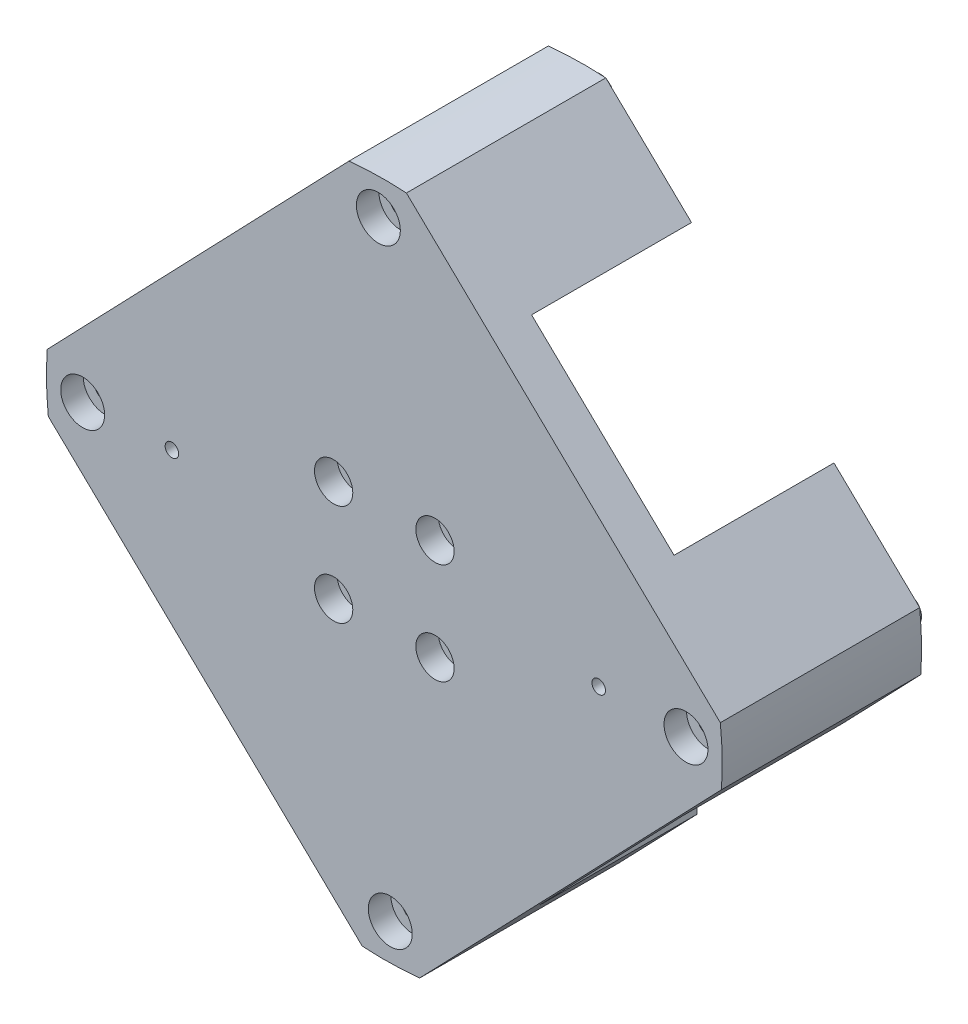
SolidWorks part; units mm, degrees
ref_plane "前视基准面" through (0, 0, 0) normal (0, 0, 1) x (1, 0, 0)
ref_plane "上视基准面" through (0, 0, 0) normal (0, 1, 0) x (1, 0, 0)
ref_plane "右视基准面" through (0, 0, 0) normal (1, 0, 0) x (0, 0, -1)
other "Configuration Table"
sketch "草图1" plane through (0, 0, 0) normal (0, 0, 1) x (1, 0, 0)
  circle A0 centre (9, 9) radius 2.6 construction
  circle A1 centre (9, -9) radius 2.6
  circle A2 centre (9, -9) radius 2.6
  circle A3 centre (0, 0) radius 60
  circle A4 centre (0, 0) radius 60
  circle A5 centre (9, 9) radius 1.4 construction
  circle A6 centre (-9, 9) radius 1.4 construction
  circle A7 centre (-9, 9) radius 2.6 construction
  circle A8 centre (-9, -9) radius 1.4 construction
  circle A9 centre (-9, -9) radius 2.6 construction
  circle A10 centre (9, 9) radius 2.6
  circle A11 centre (9, 9) radius 1.4
  circle A12 centre (-9, 9) radius 1.4
  circle A13 centre (-9, 9) radius 2.6
  circle A14 centre (-9, -9) radius 1.4
  circle A15 centre (-9, -9) radius 2.6
  circle A16 centre (9, -9) radius 1.4 construction
  circle A17 centre (9, -9) radius 1.4
  circle A18 centre (0, 0) radius 47.6 construction
  circle A19 centre (0, 0) radius 47.6
  circle A20 centre (53.5645, 1.0586) radius 2.425 construction
  circle A21 centre (53.5645, 1.0586) radius 2.425
  circle A22 centre (1.0586, -53.5645) radius 2.425 construction
  circle A23 centre (1.0586, -53.5645) radius 2.425
  circle A24 centre (-53.5645, -1.0586) radius 2.425 construction
  circle A25 centre (-53.5645, -1.0586) radius 2.425
  circle A26 centre (-1.0586, 53.5645) radius 2.425 construction
  circle A27 centre (-1.0586, 53.5645) radius 2.425
  dimension "D1" = 0
  dimension "D2" = 0
extrude "凸台-拉伸1" add sketch "草图1" along normal blind 3 contours A4 A27 A25 A23 A21 A19 | A19 A2 A10 A13 A15 region at (-58.3029, 0, 0) region at (0, 0, 0)
sketch "草图2" plane through (0, 0, 0) normal (0, 0, -1) x (-1, 0, 0)
  circle A0 centre (0, 0) radius 47.6 construction
  circle A1 centre (0, 0) radius 60
  circle A2 centre (0, 0) radius 60
  circle A3 centre (0, 0) radius 47.6
  circle A4 centre (1.0586, 53.5645) radius 2.425 construction
  circle A5 centre (1.0586, 53.5645) radius 2.425
  circle A6 centre (-53.5645, 1.0586) radius 2.425 construction
  circle A7 centre (-53.5645, 1.0586) radius 2.425
  circle A8 centre (-1.0586, -53.5645) radius 2.425 construction
  circle A9 centre (-1.0586, -53.5645) radius 2.425
  circle A10 centre (53.5645, -1.0586) radius 2.425 construction
  circle A11 centre (53.5645, -1.0586) radius 2.425
  dimension "D1" = 0
extrude "凸台-拉伸2" add sketch "草图2" along normal up to surface (28.4 mm away) contours A2 | A5 | A9 | A7 | A11 | A3
sketch "草图3" plane through (0, 0, 3) normal (0, 0, 1) x (1, 0, 0)
  line L0 (-53.5645, -1.0586) -> (-1.0586, 53.5645)
  line L1 (-53.5645, -1.0586) -> (1.0586, -53.5645)
  line L2 (-1.0586, 53.5645) -> (53.5645, 1.0586)
  line L3 (1.0586, -53.5645) -> (53.5645, 1.0586)
  line L4 (-64.876, -1.2822) -> (-1.2822, 64.876)
  line L5 (-1.2822, 64.876) -> (64.876, 1.2822)
  line L6 (1.2822, -64.876) -> (64.876, 1.2822)
  line L7 (-64.876, -1.2822) -> (1.2822, -64.876)
  circle A0 centre (53.5645, 1.0586) radius 2.425 construction
  circle A1 centre (0, 0) radius 60
  circle A2 centre (0, 0) radius 60
  circle A3 centre (53.5645, 1.0586) radius 2.425
  circle A4 centre (-1.0586, 53.5645) radius 2.425 construction
  circle A5 centre (-1.0586, 53.5645) radius 2.425
  circle A6 centre (-53.5645, -1.0586) radius 2.425 construction
  circle A7 centre (-53.5645, -1.0586) radius 2.425
  circle M10 centre (0, 0) radius 60
  dimension "D1" = 0
  dimension "D2" = 8
extrude "切除-拉伸1" cut sketch "草图3" against normal blind 31 contours L4 M10 | L7 M10 | L5 M10 | L6 M10 region at (-37.1941, 35.7524, 3) region at (-35.7524, -37.1941, 3) region at (35.7524, 37.1941, 3) region at (37.1941, -35.7524, 3)
sketch "草图4" plane through (0, 0, -28) normal (0, 0, 1) x (1, 0, 0)
  line L2 (40.9301, 24.3) -> (59.6697, 6.2867)
  line L3 (3.9241, 59.8715) -> (22.6638, 41.8583)
  line L4 (40.9301, 24.3) -> (59.6697, 6.2867)
  line L5 (3.9241, 59.8715) -> (22.6638, 41.8583)
  line L6 (24.3, -40.9301) -> (6.2867, -59.6697)
  line L7 (59.8715, -3.9241) -> (41.8583, -22.6638)
  line L8 (24.3, -40.9301) -> (6.2867, -59.6697)
  line L9 (59.8715, -3.9241) -> (41.8583, -22.6638)
  line L10 (-40.9301, -24.3) -> (-59.6697, -6.2867)
  line L11 (-3.9241, -59.8715) -> (-22.6638, -41.8583)
  line L12 (-40.9301, -24.3) -> (-59.6697, -6.2867)
  line L13 (-3.9241, -59.8715) -> (-22.6638, -41.8583)
  line L14 (-24.3, 40.9301) -> (-6.2867, 59.6697)
  line L15 (-59.8715, 3.9241) -> (-41.8583, 22.6638)
  line L16 (-24.3, 40.9301) -> (-6.2867, 59.6697)
  line L17 (-59.8715, 3.9241) -> (-41.8583, 22.6638)
  arc A2 (59.6697, 6.2867) -> (3.9241, 59.8715) centre (0, 0) ccw
  arc A3 (40.9301, 24.3) -> (22.6638, 41.8583) centre (0, 0) ccw
  arc A4 (59.6697, 6.2867) -> (3.9241, 59.8715) centre (0, 0) ccw
  arc A5 (40.9301, 24.3) -> (22.6638, 41.8583) centre (0, 0) ccw
  arc A6 (6.2867, -59.6697) -> (59.8715, -3.9241) centre (0, 0) ccw
  arc A7 (24.3, -40.9301) -> (41.8583, -22.6638) centre (0, 0) ccw
  arc A8 (6.2867, -59.6697) -> (59.8715, -3.9241) centre (0, 0) ccw
  arc A9 (24.3, -40.9301) -> (41.8583, -22.6638) centre (0, 0) ccw
  arc A10 (-59.6697, -6.2867) -> (-3.9241, -59.8715) centre (0, 0) ccw
  arc A11 (-40.9301, -24.3) -> (-22.6638, -41.8583) centre (0, 0) ccw
  arc A12 (-59.6697, -6.2867) -> (-3.9241, -59.8715) centre (0, 0) ccw
  arc A13 (-40.9301, -24.3) -> (-22.6638, -41.8583) centre (0, 0) ccw
  arc A14 (-6.2867, 59.6697) -> (-59.8715, 3.9241) centre (0, 0) ccw
  arc A15 (-24.3, 40.9301) -> (-41.8583, 22.6638) centre (0, 0) ccw
  arc A16 (-6.2867, 59.6697) -> (-59.8715, 3.9241) centre (0, 0) ccw
  arc A17 (-24.3, 40.9301) -> (-41.8583, 22.6638) centre (0, 0) ccw
  dimension "D1" = 0
  dimension "D2" = 0
  dimension "D3" = 0
  dimension "D4" = 0
extrude "切除-拉伸2" cut sketch "草图4" against normal up to next
chamfer "倒角1" distance 6 angle 45 8 edges at (-24.3, 40.9301, -14.2) (-41.8583, 22.6638, -14.2) (-40.9301, -24.3, -14.2) (-22.6638, -41.8583, -14.2) (24.3, -40.9301, -14.2) (41.8583, -22.6638, -14.2) (40.9301, 24.3, -14.2) (22.6638, 41.8583, -14.2) first distance on face at (-0.8793, 44.4924, -14.2) first distance on face at (-44.4924, -0.8793, -14.2) first distance on face at (-31.7969, -33.0791, -13.45) first distance on face at (33.0791, -31.7969, -13.45) first distance on face at (44.4924, 0.8793, -14.2)
sketch "草图6" plane through (0, 0, 3) normal (0, 0, 1) x (1, 0, 0)
  line L4 (-59.6697, -6.2867) -> (-3.9241, -59.8715)
  line L5 (6.2867, -59.6697) -> (59.8715, -3.9241)
  line L6 (59.6697, 6.2867) -> (3.9241, 59.8715)
  line L7 (-6.2867, 59.6697) -> (-59.8715, 3.9241)
  line L8 (-59.6697, -6.2867) -> (-3.9241, -59.8715)
  line L9 (6.2867, -59.6697) -> (59.8715, -3.9241)
  line L10 (59.6697, 6.2867) -> (3.9241, 59.8715)
  line L11 (-6.2867, 59.6697) -> (-59.8715, 3.9241)
  circle A0 centre (9, 9) radius 2.6 construction
  circle A1 centre (9, 9) radius 2.6
  circle A2 centre (9, -9) radius 2.6 construction
  circle A3 centre (9, -9) radius 2.6
  arc A4 (-59.8715, 3.9241) -> (-59.6697, -6.2867) centre (0, 0) ccw
  arc A5 (-3.9241, -59.8715) -> (6.2867, -59.6697) centre (0, 0) ccw
  arc A6 (59.8715, -3.9241) -> (59.6697, 6.2867) centre (0, 0) ccw
  arc A7 (3.9241, 59.8715) -> (-6.2867, 59.6697) centre (0, 0) ccw
  arc A8 (-59.8715, 3.9241) -> (-59.6697, -6.2867) centre (0, 0) ccw
  arc A9 (-3.9241, -59.8715) -> (6.2867, -59.6697) centre (0, 0) ccw
  arc A10 (59.8715, -3.9241) -> (59.6697, 6.2867) centre (0, 0) ccw
  arc A11 (3.9241, 59.8715) -> (-6.2867, 59.6697) centre (0, 0) ccw
  circle A12 centre (-9, -9) radius 2.6 construction
  circle A13 centre (-9, -9) radius 2.6
  circle A14 centre (-9, 9) radius 2.6 construction
  circle A15 centre (-9, 9) radius 2.6
  circle A16 centre (-9, 9) radius 1.4 construction
  circle A17 centre (-9, 9) radius 1.4
  circle A18 centre (9, 9) radius 1.4 construction
  circle A19 centre (9, 9) radius 1.4
  circle A20 centre (9, -9) radius 1.4 construction
  circle A21 centre (9, -9) radius 1.4
  circle A22 centre (-9, -9) radius 1.4 construction
  circle A23 centre (-9, -9) radius 1.4
  circle M17 centre (9, -9) radius 2.6
  circle M18 centre (9, 9) radius 2.6
  circle M19 centre (-9, 9) radius 2.6
  circle M20 centre (-9, -9) radius 2.6
  dimension "D1" = 0
extrude "凸台-拉伸4" add sketch "草图6" against normal up to surface (3 mm away) contours A19 M18 | A21 M17 | A23 M20 | A17 M19 region at (6.4735, 9, 3) region at (6.4735, -9, 3) region at (-11.5265, -9, 3) region at (-11.5265, 9, 3) up to face at (-6.4, -9, 0)
sketch "草图7" plane through (0, 0, 0) normal (0, 0, -1) x (-1, 0, 0)
  line L12 (18.3381, -46.0162) -> (45.2557, -20.142)
  line L13 (45.2557, -20.142) -> (43.1478, -20.1003)
  line L14 (44.5387, 16.7948) -> (45.2385, 19.1472)
  line L15 (45.2385, 19.1472) -> (20.9197, 44.4466)
  line L16 (20.9197, 44.4466) -> (18.5415, 43.8403)
  line L17 (-16.7948, 44.5387) -> (-19.1472, 45.2385)
  line L18 (-19.1472, 45.2385) -> (-44.4466, 20.9197)
  line L19 (-44.4466, 20.9197) -> (-43.8403, 18.5415)
  line L20 (-43.9084, -18.3798) -> (-46.0162, -18.3381)
  line L21 (-46.0162, -18.3381) -> (-20.142, -45.2557)
  line L22 (-20.142, -45.2557) -> (-20.1003, -43.1478)
  line L23 (18.3798, -43.9084) -> (18.3381, -46.0162)
  line L24 (18.3381, -46.0162) -> (45.2557, -20.142)
  line L25 (45.2557, -20.142) -> (43.1478, -20.1003)
  line L26 (44.5387, 16.7948) -> (45.2385, 19.1472)
  line L27 (45.2385, 19.1472) -> (20.9197, 44.4466)
  line L28 (20.9197, 44.4466) -> (18.5415, 43.8403)
  line L29 (-16.7948, 44.5387) -> (-19.1472, 45.2385)
  line L30 (-19.1472, 45.2385) -> (-44.4466, 20.9197)
  line L31 (-44.4466, 20.9197) -> (-43.8403, 18.5415)
  line L32 (-43.9084, -18.3798) -> (-46.0162, -18.3381)
  line L33 (-46.0162, -18.3381) -> (-20.142, -45.2557)
  line L34 (-20.142, -45.2557) -> (-20.1003, -43.1478)
  line L35 (18.3798, -43.9084) -> (18.3381, -46.0162)
  circle A0 centre (37.7185, -0.4693) radius 1.2 construction
  circle A1 centre (37.7185, -0.4693) radius 1.2
  circle A2 centre (-38.0667, 1.0285) radius 1.2 construction
  circle A3 centre (-38.0667, 1.0285) radius 1.2
  arc A4 (43.1478, -20.1003) -> (44.5387, 16.7948) centre (0, 0) ccw
  arc A5 (18.5415, 43.8403) -> (-16.7948, 44.5387) centre (0, 0) ccw
  arc A6 (-43.8403, 18.5415) -> (-43.9084, -18.3798) centre (0, 0) ccw
  arc A7 (-20.1003, -43.1478) -> (18.3798, -43.9084) centre (0, 0) ccw
  arc A8 (43.1478, -20.1003) -> (44.5387, 16.7948) centre (0, 0) ccw
  arc A9 (18.5415, 43.8403) -> (-16.7948, 44.5387) centre (0, 0) ccw
  arc A10 (-43.8403, 18.5415) -> (-43.9084, -18.3798) centre (0, 0) ccw
  arc A11 (-20.1003, -43.1478) -> (18.3798, -43.9084) centre (0, 0) ccw
  dimension "D1" = 0
extrude "切除-拉伸3" cut sketch "草图7" against normal blind 10 contours A1 | A3
sketch "草图8" plane through (0, 0, 3) normal (0, 0, 1) x (1, 0, 0)
  line L4 (-59.6697, -6.2867) -> (-3.9241, -59.8715)
  line L5 (6.2867, -59.6697) -> (59.8715, -3.9241)
  line L6 (59.6697, 6.2867) -> (3.9241, 59.8715)
  line L7 (-6.2867, 59.6697) -> (-59.8715, 3.9241)
  line L8 (-59.6697, -6.2867) -> (-3.9241, -59.8715)
  line L9 (6.2867, -59.6697) -> (59.8715, -3.9241)
  line L10 (59.6697, 6.2867) -> (3.9241, 59.8715)
  line L11 (-6.2867, 59.6697) -> (-59.8715, 3.9241)
  circle A0 centre (-1.0586, 53.5645) radius 2.425 construction
  circle A1 centre (-1.0586, 53.5645) radius 2.425
  circle A2 centre (53.5645, 1.0586) radius 2.425 construction
  circle A3 centre (53.5645, 1.0586) radius 2.425
  arc A4 (-59.8715, 3.9241) -> (-59.6697, -6.2867) centre (0, 0) ccw
  arc A5 (-3.9241, -59.8715) -> (6.2867, -59.6697) centre (0, 0) ccw
  arc A6 (59.8715, -3.9241) -> (59.6697, 6.2867) centre (0, 0) ccw
  arc A7 (3.9241, 59.8715) -> (-6.2867, 59.6697) centre (0, 0) ccw
  arc A8 (-59.8715, 3.9241) -> (-59.6697, -6.2867) centre (0, 0) ccw
  arc A9 (-3.9241, -59.8715) -> (6.2867, -59.6697) centre (0, 0) ccw
  arc A10 (59.8715, -3.9241) -> (59.6697, 6.2867) centre (0, 0) ccw
  arc A11 (3.9241, 59.8715) -> (-6.2867, 59.6697) centre (0, 0) ccw
  circle A12 centre (1.0586, -53.5645) radius 2.425 construction
  circle A13 centre (1.0586, -53.5645) radius 2.425
  circle A14 centre (-53.5645, -1.0586) radius 2.425 construction
  circle A15 centre (-53.5645, -1.0586) radius 2.425
  circle A16 centre (-1.0586, 53.5645) radius 1.9
  circle A17 centre (-53.5645, -1.0586) radius 1.9
  circle A18 centre (53.5645, 1.0586) radius 1.9
  circle A19 centre (1.0586, -53.5645) radius 1.9
  circle M12 centre (-1.0586, 53.5645) radius 2.425
  circle M13 centre (-53.5645, -1.0586) radius 2.425
  circle M14 centre (1.0586, -53.5645) radius 2.425
  circle M15 centre (53.5645, 1.0586) radius 2.425
  dimension "D2" = 3.8
  dimension "D3" = 3.8
  dimension "D4" = 3.8
  dimension "D5" = 3.8
  dimension "D1" = 0
extrude "凸台-拉伸5" add sketch "草图8" against normal offset from surface (35.4 mm away) 4 contours A16 M12 | A17 M13 | A19 M14 | A18 M15 region at (-3.415, 53.5645, 3) region at (51.2081, 1.0586, 3) region at (-1.2978, -53.5645, 3) region at (-55.921, -1.0586, 3) up to face at (-50.2771, -1.1346, -28.4) offset beyond the face yes
sketch "草图9" plane through (0, 0, 3) normal (0, 0, 1) x (1, 0, 0)
  line L4 (-59.6697, -6.2867) -> (-3.9241, -59.8715)
  line L5 (6.2867, -59.6697) -> (59.8715, -3.9241)
  line L6 (59.6697, 6.2867) -> (3.9241, 59.8715)
  line L7 (-6.2867, 59.6697) -> (-59.8715, 3.9241)
  line L8 (-59.6697, -6.2867) -> (-3.9241, -59.8715)
  line L9 (6.2867, -59.6697) -> (59.8715, -3.9241)
  line L10 (59.6697, 6.2867) -> (3.9241, 59.8715)
  line L11 (-6.2867, 59.6697) -> (-59.8715, 3.9241)
  circle A0 centre (-1.0586, 53.5645) radius 1.9 construction
  circle A1 centre (-1.0586, 53.5645) radius 1.9
  circle A2 centre (-53.5645, -1.0586) radius 1.9 construction
  circle A3 centre (-53.5645, -1.0586) radius 1.9
  arc A4 (-59.8715, 3.9241) -> (-59.6697, -6.2867) centre (0, 0) ccw
  arc A5 (-3.9241, -59.8715) -> (6.2867, -59.6697) centre (0, 0) ccw
  arc A6 (59.8715, -3.9241) -> (59.6697, 6.2867) centre (0, 0) ccw
  arc A7 (3.9241, 59.8715) -> (-6.2867, 59.6697) centre (0, 0) ccw
  arc A8 (-59.8715, 3.9241) -> (-59.6697, -6.2867) centre (0, 0) ccw
  arc A9 (-3.9241, -59.8715) -> (6.2867, -59.6697) centre (0, 0) ccw
  arc A10 (59.8715, -3.9241) -> (59.6697, 6.2867) centre (0, 0) ccw
  arc A11 (3.9241, 59.8715) -> (-6.2867, 59.6697) centre (0, 0) ccw
  circle A12 centre (1.0586, -53.5645) radius 1.9 construction
  circle A13 centre (1.0586, -53.5645) radius 1.9
  circle A14 centre (53.5645, 1.0586) radius 1.9 construction
  circle A15 centre (53.5645, 1.0586) radius 1.9
  circle A16 centre (9, 9) radius 1.4 construction
  circle A17 centre (9, 9) radius 1.4
  circle A18 centre (-9, 9) radius 1.4 construction
  circle A19 centre (-9, 9) radius 1.4
  circle A20 centre (-9, -9) radius 1.4 construction
  circle A21 centre (-9, -9) radius 1.4
  circle A22 centre (9, -9) radius 1.4 construction
  circle A23 centre (9, -9) radius 1.4
  circle A24 centre (-37.7185, -0.4693) radius 1.2 construction
  circle A25 centre (-37.7185, -0.4693) radius 1.2
  circle A26 centre (38.0667, 1.0285) radius 1.2 construction
  circle A27 centre (38.0667, 1.0285) radius 1.2
  circle A28 centre (-53.5645, -1.0586) radius 3.9
  circle A29 centre (-1.0586, 53.5645) radius 3.9
  circle A30 centre (53.5645, 1.0586) radius 3.9
  circle A31 centre (9, 9) radius 3.4
  circle A32 centre (-9, 9) radius 3.4
  circle A33 centre (-9, -9) radius 3.4
  circle A34 centre (9, -9) radius 3.4
  circle A35 centre (1.0586, -53.5645) radius 3.9
  circle M12 centre (-37.7185, -0.4693) radius 1.2
  circle M13 centre (38.0667, 1.0285) radius 1.2
  arc M14 (-59.8715, 3.9241) -> (-59.6697, -6.2867) centre (0, 0) ccw
  line M15 (-59.6697, -6.2867) -> (-3.9241, -59.8715)
  arc M16 (-3.9241, -59.8715) -> (6.2867, -59.6697) centre (0, 0) ccw
  line M17 (6.2867, -59.6697) -> (59.8715, -3.9241)
  arc M18 (59.8715, -3.9241) -> (59.6697, 6.2867) centre (0, 0) ccw
  line M19 (59.6697, 6.2867) -> (3.9241, 59.8715)
  arc M20 (3.9241, 59.8715) -> (-6.2867, 59.6697) centre (0, 0) ccw
  line M21 (-6.2867, 59.6697) -> (-59.8715, 3.9241)
  dimension "D1" = 0
  dimension "D2" = 2
extrude "凸台-拉伸6" add sketch "草图9" along normal blind 4 contours A35 A34 A33 A32 A31 A30 A29 A28 M21 M14 M15 M16 M17 M18 M19 M20 M13 M12 region at (-0.0002, -0.0003, 3)
